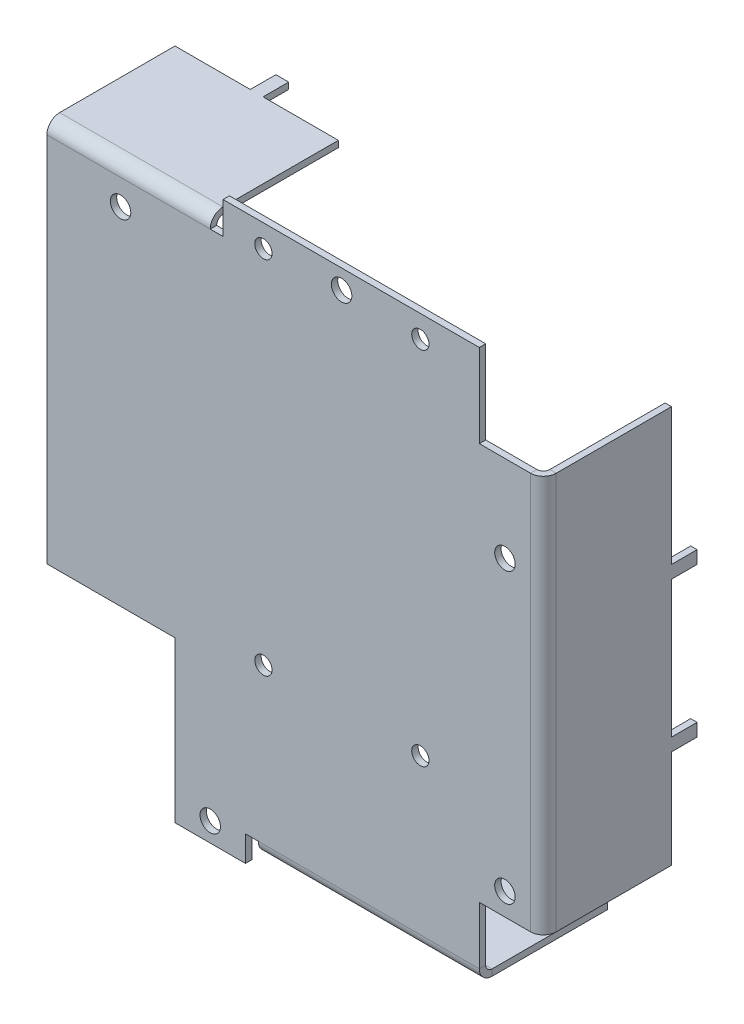
SolidWorks part; units mm, degrees
note: The reader was unsure of these and kept them because the rebuilt part matched: flange length of "Edge-Flange1".
ref_plane "Front Plane" through (0, 0, 0) normal (0, 0, 1) x (1, 0, 0)
ref_plane "Top Plane" through (0, 0, 0) normal (0, 1, 0) x (1, 0, 0)
ref_plane "Right Plane" through (0, 0, 0) normal (1, 0, 0) x (0, 0, -1)
sketch "Sketch1" plane through (0, 0, 10) normal (0, 0, 1) x (1, 0, 0)
  line L0 (-44.5833, -10.2016) -> (-24.5833, -10.2016)
  line L1 (-13.5833, -35.2016) -> (-24.5833, -35.2016)
  line L2 (30.9167, -22.2016) -> (30.9167, 39.7984)
  line L3 (-19.5833, 52.7984) -> (-55.0833, 52.7984) construction
  line L4 (-44.5833, -10.2016) -> (-44.5833, 47.7984)
  line L5 (30.9167, -22.2016) -> (22.9167, -22.2016)
  line L6 (22.9167, -22.2016) -> (22.9167, -31.2016)
  line L7 (-24.5833, -10.2016) -> (-24.5833, -35.2016)
  line L8 (22.9167, 52.7984) -> (22.9167, 39.7984)
  line L9 (22.9167, 39.7984) -> (30.9167, 39.7984)
  line L12 (22.9167, 52.7984) -> (-17.0833, 52.7984)
  line L13 (-17.0833, 52.7984) -> (-17.0833, 47.7984)
  line L14 (-17.0833, 47.7984) -> (-44.5833, 47.7984)
  line L15 (-13.5833, -35.2016) -> (-13.5833, -31.2016)
  line L17 (-13.5833, -31.2016) -> (22.9167, -31.2016)
  point P10 (-24.5833, -10.2016)
  dimension "D5" = 8
  dimension "D1" = 13
  dimension "D2" = 75.5
  dimension "D3" = 20
  dimension "D4" = 25
  dimension "D6" = 8
  dimension "D7" = 88
  dimension "D9" = 62
  dimension "D10" = 5
  dimension "D11" = 40
  dimension "D14" = 11
  dimension "D15" = 27.5
  dimension "D16" = 4
extrude "Boss-Extrude2" add sketch "Sketch1" along normal blind 1
hole_wizard "Ø3.2 (3.2) Diameter Hole1" positions "Sketch5" profile "Sketch4" hole size "Ø3.2" standard "Ansi Metric"
sketch "Sketch5" plane through (0, 0, 11) normal (0, 0, 1) x (1, 0, 0)
  point P0 (-33.0833, 43.7984)
  point P1 (26.9167, 26.2984)
  point P4 (26.9167, -18.7016)
  point P35 (1.4167, 49.7984)
  point P44 (-19.0833, -32.2016)
sketch "Sketch4" plane through (-33.0833, 43.7984, 11) normal (1, 0, 0) x (0, -1, 0)
  line L0 (0, 0) -> (0, 2.5614)
  line L1 (0, 2.5614) -> (1.6, 1.6)
  line L2 (1.6, 1.6) -> (1.6, 0)
  line L5 (1.6, 0) -> (0, 0)
  line L10 (0, 2.5614) -> (-1.6, 1.6) construction
  line L11 (0, -6.35) -> (0, 107.95) construction
  dimension "Hole Dia." = 3.2
  dimension "Hole Depth" = 1.6
  dimension "Drill Angle" = 118
hole_wizard "Ø2.7 (2.7) Diameter Hole1" positions "Sketch7" profile "Sketch6" hole size "Ø2.7" standard "Ansi Metric"
sketch "Sketch7" plane through (0, 0, 11) normal (0, 0, 1) x (1, 0, 0)
  line L0 (18.7167, -6.9945) -> (8.7167, -6.9945) construction
  line L1 (18.7167, -9.4945) -> (18.7167, -4.4945) construction
  line L2 (8.7167, 51.7984) -> (8.7167, -9.4945) construction
  line L4 (-15.7833, -6.9945) -> (-5.7833, -6.9945) construction
  line L5 (-15.7833, -4.4945) -> (-15.7833, -9.4945) construction
  line L6 (-5.7833, -9.4945) -> (-5.7833, 51.7984) construction
  line L8 (-15.7833, 49.2984) -> (-5.7833, 49.2984) construction
  line L9 (-15.7833, 51.7984) -> (-15.7833, 46.7984) construction
  line L10 (8.7167, 49.2984) -> (18.7167, 49.2984) construction
  line L11 (18.7167, 46.7984) -> (18.7167, 51.7984) construction
  point P0 (-10.7833, -6.9945)
  point P1 (13.7167, -6.9945)
  point P3 (-10.7833, 49.2984)
  point P5 (13.7167, 49.2984)
sketch "Sketch6" plane through (-10.7833, -6.9945, 11) normal (1, 0, 0) x (0, -1, 0)
  line L0 (0, 0) -> (0, 2.4112)
  line L1 (0, 2.4112) -> (1.35, 1.6)
  line L2 (1.35, 1.6) -> (1.35, 0)
  line L5 (1.35, 0) -> (0, 0)
  line L10 (0, 2.4112) -> (-1.35, 1.6) construction
  line L11 (0, -6.35) -> (0, 107.95) construction
  dimension "Hole Dia." = 2.7
  dimension "Hole Depth" = 1.6
  dimension "Drill Angle" = 118
sheet metal parameters "Sheet-Metal1" thickness 1 parameters "D1"=1
convert to sheet metal "Convert-Solid1" parameters "D1"=1
edge flange "Edge-Flange1" sketch "Sketch15" flange profiles "Sketch15", "Sketch17", "Sketch19" flange angle 90 flange length 23 flange position bend outside bend radius 1 thickness 1 relief rectangular parameters "D6"=10, "D8"=1
sketch "Sketch15" plane through (30.9167, 0, 10) normal (1, 0, 0) x (0, -1, 0)
  line L1 (22.2016, 0) -> (-39.7984, 0) construction
  line L2 (22.2016, 0) -> (22.2016, 19)
  line L3 (22.2016, 19) -> (6.8716, 19)
  line L4 (-39.7984, 19) -> (-39.7984, 0)
  line L5 (22.2016, 0) -> (-39.7984, 0)
  line L8 (6.8716, 19) -> (6.8716, 23)
  line L11 (6.8716, 23) -> (4.8716, 23)
  line L12 (4.8716, 23) -> (4.8716, 19)
  line L13 (-18.4684, 19) -> (-18.4684, 23)
  line L14 (-18.4684, 23) -> (-16.4684, 23)
  line L15 (-16.4684, 23) -> (-16.4684, 19)
  line L16 (-18.4684, 19) -> (-39.7984, 19)
  line L17 (4.8716, 19) -> (-16.4684, 19)
  point P10 (-18.4684, 19)
  point P21 (4.8716, 19)
  dimension "D1" = 19
  dimension "D2" = 2
  dimension "D3" = 2
  dimension "D4" = 23
  dimension "D5" = 23
  dimension "D8" = 15.33
  dimension "D9" = 21.33
sketch "Sketch17" plane through (0, 47.7984, 10) normal (0, 1, 0) x (1, 0, 0)
  line L0 (-17.0833, 0) -> (-44.5833, 0) construction
  line L1 (-19.0833, 0) -> (-44.5833, 0)
  line L2 (-44.5833, 0) -> (-44.5833, 19)
  line L3 (-44.5833, 19) -> (-32.8333, 19)
  line L4 (-19.0833, 19) -> (-19.0833, 0)
  line L5 (-32.8333, 19) -> (-32.8333, 23)
  line L6 (-32.8333, 23) -> (-30.8333, 23)
  line L7 (-30.8333, 23) -> (-30.8333, 19)
  line L8 (-30.8333, 19) -> (-19.0833, 19)
  point P14 (-30.8333, 19)
  dimension "D1" = 2
  dimension "D2" = 19
  dimension "D3" = 23
  dimension "D4" = 2
  dimension "D6" = 11.75
sketch "Sketch19" plane through (0, -31.2016, 10) normal (0, -1, 0) x (-1, 0, 0)
  line L0 (13.5833, 0) -> (-22.9167, 0) construction
  line L1 (11.5833, 0) -> (-22.9167, 0)
  line L2 (-22.9167, 0) -> (-22.9167, 19)
  line L3 (-22.9167, 19) -> (-6.6667, 19)
  line L4 (11.5833, 19) -> (11.5833, 0)
  line L5 (-4.6667, 19) -> (-4.6667, 23)
  line L8 (-4.6667, 23) -> (-6.6667, 23)
  line L11 (-6.6667, 23) -> (-6.6667, 19)
  line L12 (-4.6667, 19) -> (11.5833, 19)
  dimension "D1" = 2
  dimension "D2" = 19
  dimension "D3" = 2
  dimension "D4" = 23
  dimension "D6" = 16.25
bend "EdgeBend1" bend radius 1 bend angle 90 parameters "D5"=1
bend "EdgeBend2" bend radius 1 bend angle 90 parameters "D5"=2
bend "EdgeBend3" bend radius 1 bend angle 90 parameters "D5"=3
fillet "Fillet1" [suppressed] radius 3
fillet "Fillet2" [suppressed] radius 3
fillet "Fillet3" [suppressed] radius 1
fillet "Fillet5" [suppressed] radius 1
ref_plane "Plane2" through (0, 0, 10) normal (0, 0, -1) x (-1, 0, 0)
flat pattern "Flat-Pattern1" [suppressed]
sketch "Bend-Lines1" plane through (0, 0, 11) normal (0, 0, 1) x (1, 0, 0)
  line L0 (22.9167, -32.3797) -> (-11.5833, -32.3797) construction
  line L1 (-44.5833, 48.9765) -> (-19.0833, 48.9765) construction
  line L2 (32.0948, 39.7984) -> (32.0948, -22.2016) construction
  line L3 (22.9167, -32.3797) -> (-11.5833, -32.3797) construction
  line L4 (-44.5833, 48.9765) -> (-19.0833, 48.9765) construction
  line L5 (32.0948, 39.7984) -> (32.0948, -22.2016) construction
sketch3d "Bounding-Box1" [suppressed]
  line L0 (32.3562, 94.3562, 0) -> (32.3562, -33.3562, 0) construction
  line L1 (-67.5, 94.3562, 0) -> (-67.5, -33.3562, 0) construction
  line L2 (32.3562, 94.3562, 0) -> (-67.5, 94.3562, 0) construction
  line L3 (32.3562, -33.3562, 0) -> (-67.5, -33.3562, 0) construction
bend of the flat pattern "Flatten-<EdgeBend1>1"
bend of the flat pattern "Flatten-<EdgeBend2>1"
bend of the flat pattern "Flatten-<EdgeBend3>1"
fillet "Fillet4" [suppressed] radius 1
